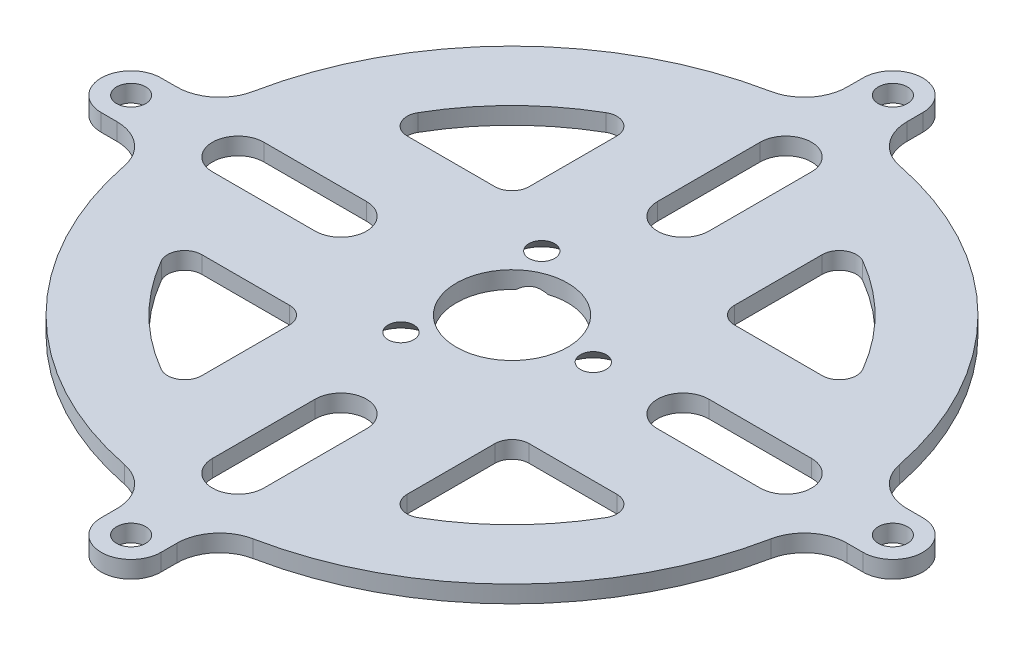
SolidWorks part; units mm, degrees
material "Thornel Mat VMA"
ref_plane "前视基准面" through (0, 0, 0) normal (0, 0, 1) x (1, 0, 0)
ref_plane "上视基准面" through (0, 0, 0) normal (0, 1, 0) x (1, 0, 0)
ref_plane "右视基准面" through (0, 0, 0) normal (1, 0, 0) x (0, 0, -1)
sketch "草图2" plane through (0, 0, 0) normal (0, 1, 0) x (1, 0, 0)
  line L0 (0, 36.746) -> (0, -40.7507) construction
  line L1 (-46.0543, 0) -> (43.2401, 0) construction
  line L2 (-4.75, -8.2272) -> (0, 0) construction
  circle A0 centre (0, 0) radius 6.5
  circle A1 centre (0, 0) radius 38.5
  circle A2 centre (9.5, 0) radius 1.5
  circle A3 centre (-4.75, -8.2272) radius 1.5
  circle A4 centre (-4.75, 8.2272) radius 1.5
  dimension "D1" = 13
  dimension "D2" = 9.5
  dimension "D3" = 3
  dimension "D5" = 77
  dimension "D6" = 120
  dimension "D7" = 9.5
  dimension "D4" = 3
extrude "凸台-拉伸1" add sketch "草图2" along normal blind 2
chamfer "倒角1" distance 2 angle 44 3 edges at (9.5, 0, 1.5) (-4.75, 0, 9.7272) (-4.75, 0, -6.7272) first distance on face at (9.5, 2, 1.5) first distance on face at (-4.75, 2, 9.7272) first distance on face at (-4.75, 2, -6.7272)
sketch "草图3" plane through (0, 0, 0) normal (0, 1, 0) x (1, 0, 0)
  line L0 (-48, 0) -> (0, 0) construction
  line L1 (-44.5, -3.5) -> (-38.3406, -3.5)
  line L2 (-44.5, 3.5) -> (-38.3406, 3.5)
  line L7 (-3.5, 44.5) -> (-3.5, 38.3406)
  line L8 (3.5, 44.5) -> (3.5, 38.3406)
  line L9 (44.5, 3.5) -> (38.3406, 3.5)
  line L10 (44.5, -3.5) -> (38.3406, -3.5)
  line L11 (3.5, -44.5) -> (3.5, -38.3406)
  line L12 (-3.5, -44.5) -> (-3.5, -38.3406)
  circle A0 centre (-44.5, 0) radius 1.7
  arc A1 (-44.5, 3.5) -> (-44.5, -3.5) centre (-44.5, 0) ccw
  arc A4 (-44.5, -3.5) -> (-41, 0) centre (-44.5, 0) ccw construction
  arc A5 (-41, 0) -> (-44.5, 3.5) centre (-44.5, 0) ccw construction
  circle A12 centre (0, 44.5) radius 1.7
  arc A13 (3.5, 44.5) -> (-3.5, 44.5) centre (0, 44.5) ccw
  arc A14 (-3.5, 38.3406) -> (3.5, 38.3406) centre (0, 0) cw
  arc A15 (-3.5, 44.5) -> (0, 41) centre (0, 44.5) ccw construction
  arc A16 (0, 41) -> (3.5, 44.5) centre (0, 44.5) ccw construction
  circle A17 centre (44.5, 0) radius 1.7
  arc A18 (44.5, -3.5) -> (44.5, 3.5) centre (44.5, 0) ccw
  arc A19 (38.3406, 3.5) -> (38.3406, -3.5) centre (0, 0) cw
  arc A20 (44.5, 3.5) -> (41, 0) centre (44.5, 0) ccw construction
  arc A21 (41, 0) -> (44.5, -3.5) centre (44.5, 0) ccw construction
  circle A22 centre (0, -44.5) radius 1.7
  arc A23 (-3.5, -44.5) -> (3.5, -44.5) centre (0, -44.5) ccw
  arc A24 (3.5, -38.3406) -> (-3.5, -38.3406) centre (0, 0) cw
  arc A25 (3.5, -44.5) -> (0, -41) centre (0, -44.5) ccw construction
  arc A26 (0, -41) -> (-3.5, -44.5) centre (0, -44.5) ccw construction
  circle A27 centre (0, 0) radius 38.5 construction
  arc A28 (-38.3406, -3.5) -> (-38.3406, 3.5) centre (0, 0) cw
  dimension "D1" = 3.4
  dimension "D2" = 44.5
  dimension "D3" = 7
  dimension "D4" = 4
extrude "凸台-拉伸2" add sketch "草图3" along normal blind 2 contours L9 A19 L10 A18 A17 | L7 A14 L8 A13 A12 | L11 A24 L12 A23 A22 | L1 A28 L2 A1 A0 region at (-42.6029, 0, 0) region at (0, 0, -42.6029) region at (42.6029, 0, 0) region at (0, 0, 42.6029)
fillet "圆角1" radius 5 8 edges at (-38.3406, 1, -3.5) (-38.3406, 1, 3.5) (-3.5, 1, 38.3406) (3.5, 1, 38.3406) (38.3406, 1, 3.5) (38.3406, 1, -3.5) (3.5, 1, -38.3406) (-3.5, 1, -38.3406)
sketch "草图4" plane through (0, 2, 0) normal (0, 1, 0) x (1, 0, 0)
  line L0 (-44.5, 0) -> (44.5, 0) construction
  line L1 (0, 44.5) -> (0, -44.5) construction
  line L2 (-12, 27.4955) -> (-12, 12)
  line L3 (-27.4955, 12) -> (-12, 12)
  line L4 (-27.4955, -12) -> (-12, -12)
  line L5 (12, 27.4955) -> (12, 12)
  line L6 (-12, -12) -> (-12, -27.4955)
  line L7 (-12, 12) -> (-12, 0) construction
  line L8 (12, 12) -> (27.4955, 12)
  line L9 (-12, 12) -> (0, 12) construction
  line L10 (0, 12) -> (12, 12) construction
  line L11 (12, -12) -> (12, -27.4955)
  line L12 (12, 12) -> (12, 0) construction
  line L13 (12, 0) -> (12, -12) construction
  line L14 (12, -12) -> (27.4955, -12)
  line L15 (0, -12) -> (12, -12) construction
  line L16 (-12, -12) -> (0, -12) construction
  line L17 (-12, 0) -> (-12, -12) construction
  arc A1 (-12, 27.4955) -> (-27.4955, 12) centre (0, 0) ccw
  arc A2 (0, 30) -> (-12, 27.4955) centre (0, 0) ccw construction
  arc A3 (12, 27.4955) -> (0, 30) centre (0, 0) ccw construction
  arc A4 (27.4955, 12) -> (12, 27.4955) centre (0, 0) ccw
  arc A5 (27.4955, -12) -> (30, 0) centre (0, 0) ccw construction
  arc A6 (12, -27.4955) -> (27.4955, -12) centre (0, 0) ccw
  arc A7 (0, -30) -> (12, -27.4955) centre (0, 0) ccw construction
  arc A8 (-12, -27.4955) -> (0, -30) centre (0, 0) ccw construction
  arc A9 (-27.4955, -12) -> (-12, -27.4955) centre (0, 0) ccw
  arc A10 (-30, 0) -> (-27.4955, -12) centre (0, 0) ccw construction
  arc A11 (-27.4955, 12) -> (-30, 0) centre (0, 0) ccw construction
  arc A12 (30, 0) -> (27.4955, 12) centre (0, 0) ccw construction
  dimension "D2" = 60
  dimension "D3" = 24
  dimension "D4" = 24
extrude "切除-拉伸1" cut sketch "草图4" against normal blind 10
fillet "圆角2" radius 2 12 edges at (-27.4955, 1, 12) (-12, 1, 12) (-12, 1, 27.4955) (12, 1, 27.4955) (27.4955, 1, 12) (12, 1, 12) (27.4955, 1, -12) (12, 1, -12) (12, 1, -27.4955) (-12, 1, -12) (-12, 1, -27.4955) (-27.4955, 1, -12)
sketch "草图5" plane through (0, 2, 0) normal (0, 1, 0) x (1, 0, 0)
  line L0 (-44.5, 0) -> (44.5, 0) construction
  line L1 (0, 44.5) -> (0, -44.5) construction
  line L2 (0, 32) -> (0, 20) construction
  line L3 (3, 32) -> (3, 20)
  line L4 (-3, 32) -> (-3, 20)
  line L5 (27.2236, 27.2236) -> (-27.2236, -27.2236) construction
  line L6 (-27.2236, 27.2236) -> (27.2236, -27.2236) construction
  line L7 (32, 0) -> (20, 0) construction
  line L8 (32, 3) -> (20, 3)
  line L9 (32, -3) -> (20, -3)
  line L10 (0, -32) -> (0, -20) construction
  line L11 (-3, -32) -> (-3, -20)
  line L12 (3, -32) -> (3, -20)
  line L13 (-32, 0) -> (-20, 0) construction
  line L14 (-32, -3) -> (-20, -3)
  line L15 (-32, 3) -> (-20, 3)
  arc A0 (3, 32) -> (-3, 32) centre (0, 32) ccw
  arc A1 (-3, 20) -> (3, 20) centre (0, 20) ccw
  arc A2 (37.7578, 7.523) -> (7.523, 37.7578) centre (0, 0) ccw construction
  arc A3 (-37.7578, -7.523) -> (-7.523, -37.7578) centre (0, 0) ccw construction
  arc A4 (-7.523, 37.7578) -> (-37.7578, 7.523) centre (0, 0) ccw construction
  arc A5 (7.523, -37.7578) -> (37.7578, -7.523) centre (0, 0) ccw construction
  arc A6 (32, 3) -> (32, -3) centre (32, 0) cw
  arc A7 (20, -3) -> (20, 3) centre (20, 0) cw
  arc A8 (-3, -32) -> (3, -32) centre (0, -32) ccw
  arc A9 (3, -20) -> (-3, -20) centre (0, -20) ccw
  arc A10 (-32, -3) -> (-32, 3) centre (-32, 0) cw
  arc A11 (-20, 3) -> (-20, -3) centre (-20, 0) cw
  point P10 (0, 26)
  point P34 (26, 0)
  point P41 (0, -26)
  point P48 (-26, 0)
  dimension "D2" = 3
  dimension "D1" = 12
  dimension "D3" = 26
extrude "切除-拉伸4" cut sketch "草图5" against normal blind 10
